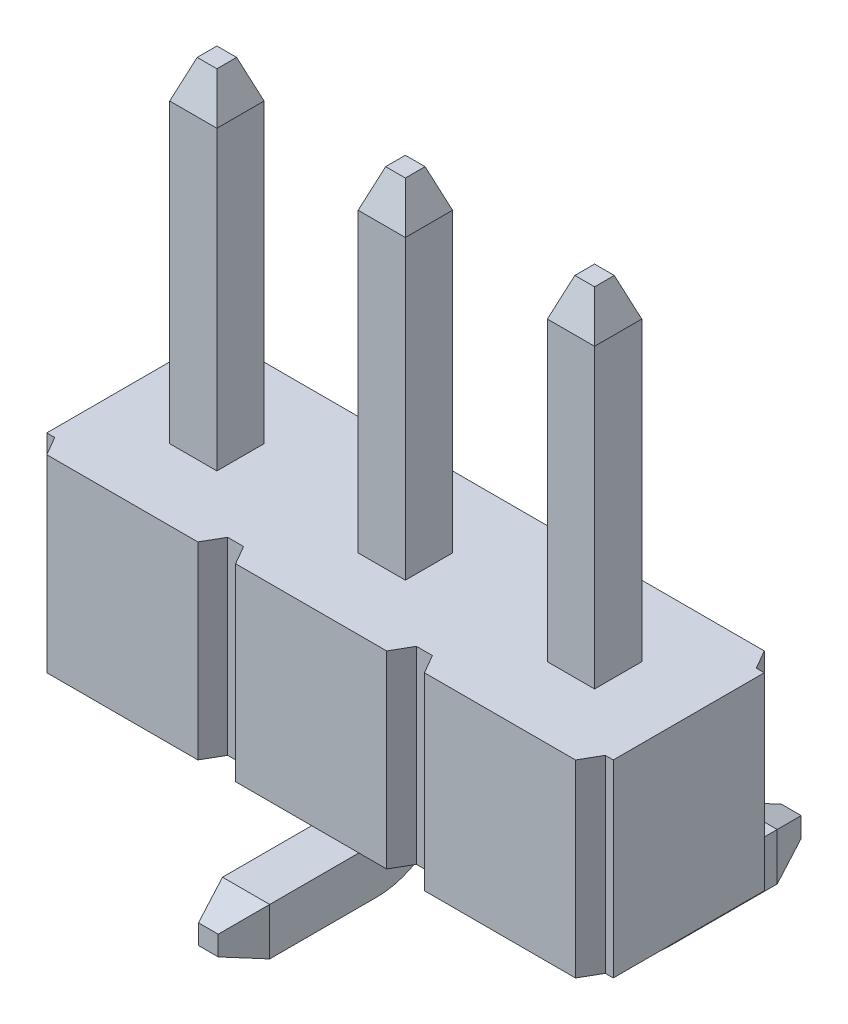
SolidWorks part; units mm, degrees
note: '?' marks a value the reader was unsure of.
ref_plane "Front" through (0, 0, 0) normal (0, 0, 1) x (1, 0, 0)
ref_plane "Top" through (0, 0, 0) normal (0, 1, 0) x (1, 0, 0)
ref_plane "Side" through (0, 0, 0) normal (1, 0, 0) x (0, 0, -1)
ref_plane "Plane for Single Option" through (2.54, 0, 0) normal (1, 0, 0) x (0, 0, -1)
ref_plane "Mid Plane" through (6.35, 0, 0) normal (1, 0, 0) x (0, 0, -1)
ref_axis "V Axis" through (0, -1.3049, 0) along (0, 1, 0)?
ref_axis "H Axis" through (0, 0, -2.8674) along (0, 0, 1)?
sketch "Sketch1" plane through (0, 0, 0) normal (0, 1, 0) x (1, 0, 0)
  line L0 (-1.27, 1.27) -> (1.27, 1.27) construction
  line L1 (-1.27, 1.27) -> (-1.27, -1.27) construction
  line L2 (1.27, -1.27) -> (-1.27, -1.27) construction
  line L3 (1.27, -1.27) -> (1.27, 1.27) construction
  line L4 (-1.27, -1.27) -> (1.27, 1.27) construction
  line L5 (-1.27, 1.27) -> (13.97, 1.27)
  line L6 (-1.27, 1.27) -> (-1.27, -1.27)
  line L7 (-1.27, -1.27) -> (13.97, -1.27)
  line L8 (13.97, -1.27) -> (13.97, 1.27)
  line L9 (1.0795, -1.27) -> (-1.0795, -1.27) construction
  line L10 (1.0795, -1.27) -> (1.0795, 1.27) construction
  dimension "D1" = 2.54
  dimension "D2" = 2.54
  dimension "D3" = 0.1905
  dimension "D4" = 15.24
extrude "Base Extrude" add sketch "Sketch1" along normal mid plane 2.54
sketch "Sketch8" plane through (0, 0, 0) normal (1, 0, 0) x (0, 0, -1)
  line L0 (-1.27, 1.27) -> (1.27, 1.27) construction
  line L1 (0.32, -1.087) -> (0.32, 5.262)
  line L3 (-0.315, -1.214) -> (-0.315, 5.262)
  line L4 (0.828, -1.595) -> (2.142, -1.595)
  line L5 (0.0025, 0) -> (0.0025, 0.5566) construction
  line L6 (-0.315, 5.262) -> (-0.1301, 5.77)
  line L7 (-0.1301, 5.77) -> (0.1351, 5.77)
  line L8 (0.1351, 5.77) -> (0.32, 5.262)
  line L9 (-0.315, 5.262) -> (0.32, 5.262) construction
  line L13 (0, -1.3049) -> (0, 1.3051) construction
  line L18 (0.701, -2.23) -> (2.142, -2.23)
  line L19 (2.65, -2.0451) -> (2.65, -1.7799)
  line L20 (3.683, -1.9125) -> (3.2473, -1.9125) construction
  line L24 (2.142, -1.595) -> (2.65, -1.7799)
  line L25 (2.142, -1.595) -> (2.142, -2.23) construction
  line L26 (2.142, -2.23) -> (2.65, -2.0451)
  arc A0 (-0.315, -1.214) -> (0.701, -2.23) centre (0.701, -1.214) ccw
  arc A1 (0.32, -1.087) -> (0.828, -1.595) centre (0.828, -1.087) ccw
  dimension "D10" = 1.016
  dimension "D11" = 0.508
  dimension "D1" = 0.508
  dimension "D2" = 70
  dimension "D3" = 4.5
  dimension "D4" = 0.0025
  dimension "D5" = 0.635
  dimension "D6" = 3.5
  dimension "D8" = 0.508
  dimension "D9" = 70
  dimension "Pin" = 2.65
extrude "Pin" add sketch "Sketch8" along normal mid plane 0.635
chamfer "Pin Chamfer" distance 0.508 angle 20 12 edges at (0.3175, -2.1376, -2.396) (0.3175, -1.9125, -2.65) (0.3175, -1.6874, -2.396) (-0.3175, 5.516, -0.2276) (-0.3175, 5.77, -0.0025) (-0.3175, 5.516, 0.2225) (-0.3175, -2.1376, -2.396) (-0.3175, -1.9125, -2.65) (-0.3175, -1.6874, -2.396) (0.3175, 5.516, -0.2276) (0.3175, 5.77, -0.0025) (0.3175, 5.516, 0.2225)
pattern_linear "Pin Pattern" count 3 spacing 5.08 along (1, 0, 0) of "Pin", "Pin Chamfer"
sketch "Sketch9" plane through (2.54, 0, 0) normal (1, 0, 0) x (0, 0, -1)
  line L1 (-0.32, -1.087) -> (-0.32, 5.262)
  line L3 (0.315, -1.214) -> (0.315, 5.262)
  line L4 (-0.32, 5.262) -> (0.315, 5.262) construction
  line L6 (0, -1.3049) -> (0, 1.3051) construction
  line L7 (-1.27, 1.27) -> (1.27, 1.27) construction
  line L8 (-0.0025, 0) -> (-0.0025, 1.0301) construction
  line L10 (-0.32, 5.262) -> (-0.1351, 5.77)
  line L11 (-0.1351, 5.77) -> (0.1301, 5.77)
  line L12 (0.1301, 5.77) -> (0.315, 5.262)
  line L18 (-0.701, -2.23) -> (-2.1445, -2.23)
  line L19 (-0.828, -1.595) -> (-2.1445, -1.595)
  line L20 (-2.1445, -1.595) -> (-2.6525, -1.7799)
  line L21 (-2.6525, -1.7799) -> (-2.6525, -2.0451)
  line L22 (-2.6525, -2.0451) -> (-2.1445, -2.23)
  line L23 (-2.1445, -1.595) -> (-2.1445, -2.23) construction
  line L24 (-2.6525, -1.9125) -> (-5.1592, -1.9125) construction
  arc A0 (-0.32, -1.087) -> (-0.828, -1.595) centre (-0.828, -1.087) cw
  arc A1 (0.315, -1.214) -> (-0.701, -2.23) centre (-0.701, -1.214) cw
  dimension "D10" = 0.508
  dimension "D11" = 1.016
  dimension "D1" = 0.0025
  dimension "D2" = 0.635
  dimension "D3" = 4.5
  dimension "D4" = 0.508
  dimension "D5" = 0.508
  dimension "D6" = 70
  dimension "D7" = 70
  dimension "D8" = 3.5
  dimension "D9" = 2.65
extrude "Pin 2" add sketch "Sketch9" along normal mid plane 0.635
chamfer "Pin 2 Chamfer" distance 0.508 angle 20 12 edges at (2.8575, -1.6874, 2.3985) (2.8575, -1.9125, 2.6525) (2.8575, -2.1376, 2.3985) (2.2225, 5.516, 0.2276) (2.2225, -1.6874, 2.3985) (2.2225, -1.9125, 2.6525) (2.2225, -2.1376, 2.3985) (2.2225, 5.516, -0.2225) (2.2225, 5.77, 0.0025) (2.8575, 5.516, -0.2225) (2.8575, 5.77, 0.0025) (2.8575, 5.516, 0.2276)
pattern_linear "Pin 2 Pattern" count 3 spacing 5.08 along (1, 0, 0) of "Pin 2", "Pin 2 Chamfer"
sketch "Sketch15" plane through (0, 1.27, 0) normal (0, 1, 0) x (-1, 0, 0)
  line L0 (-3.556, 1.27) -> (-3.7026, 1.016)
  line L1 (-3.9174, 1.016) -> (-4.064, 1.27)
  line L2 (-4.064, -1.27) -> (-3.9174, -1.016)
  line L3 (-3.7026, 1.016) -> (-3.9174, 1.016)
  line L4 (-3.9174, -1.016) -> (-3.7026, -1.016)
  line L5 (-3.7026, -1.016) -> (-3.556, -1.27)
  line L6 (-4.064, 1.27) -> (-3.556, 1.27)
  line L7 (-4.064, -1.27) -> (-3.556, -1.27)
  line L8 (-3.81, -1.27) -> (-3.81, 1.27) construction
  line L9 (1.27, -1.27) -> (1.27, 1.27) construction
  line L10 (1.27, 1.27) -> (-13.97, 1.27) construction
  line L11 (1.27, -1.27) -> (-13.97, -1.27) construction
  dimension "D1" = 5.08
  dimension "D2" = 0.254
  dimension "D3" = 0.254
  dimension "D4" = 60
  dimension "D5" = 60
  dimension "D6" = 0.2147
extrude "SV Cut" cut sketch "Sketch15" against normal through all
pattern_linear "SV Cut Pattern" count 5 spacing 2.54 along (1, 0, 0) of "SV Cut"
ref_plane "Polarize Plane -S" through (2.54, 0, 0) normal (1, 0, 0) x (0, 0, -1)
ref_plane "Polarize Plane -D" through (2.54, 0, 0) normal (1, 0, 0) x (0, 0, -1)
ref_plane "Polarize Plane-H" through (2.54, 0, 0) normal (1, 0, 0) x (0, 0, -1)
ref_plane "Polarize Plane-HD" through (2.54, 0, 0) normal (1, 0, 0) x (0, 0, -1)
pattern_linear "LPattern1" count 3 spacing 2.54 along (-1, 0, 0) of "SV Cut"
sketch "Sketch16" plane through (0, 5.77, 0) normal (0, 1, 0) x (1, 0, 0)
  line L0 (13.97, -1.016) -> (13.97, 1.016) construction
  line L1 (6.35, 2.65) -> (13.97, 2.65)
  line L2 (6.35, 2.65) -> (6.35, -2.6525)
  line L3 (6.35, -2.6525) -> (13.97, -2.6525)
  line L4 (13.97, 2.65) -> (13.97, -2.6525)
  line L5 (10.2926, 2.65) -> (10.0274, 2.65) construction
  line L6 (7.7526, -2.6525) -> (7.4874, -2.6525) construction
  line L7 (6.35, 1.016) -> (6.35, 0.4722) construction
  line L8 (6.2426, 1.016) -> (6.4574, 1.016) construction
extrude "Cut-Extrude1" cut sketch "Sketch16" against normal through all
